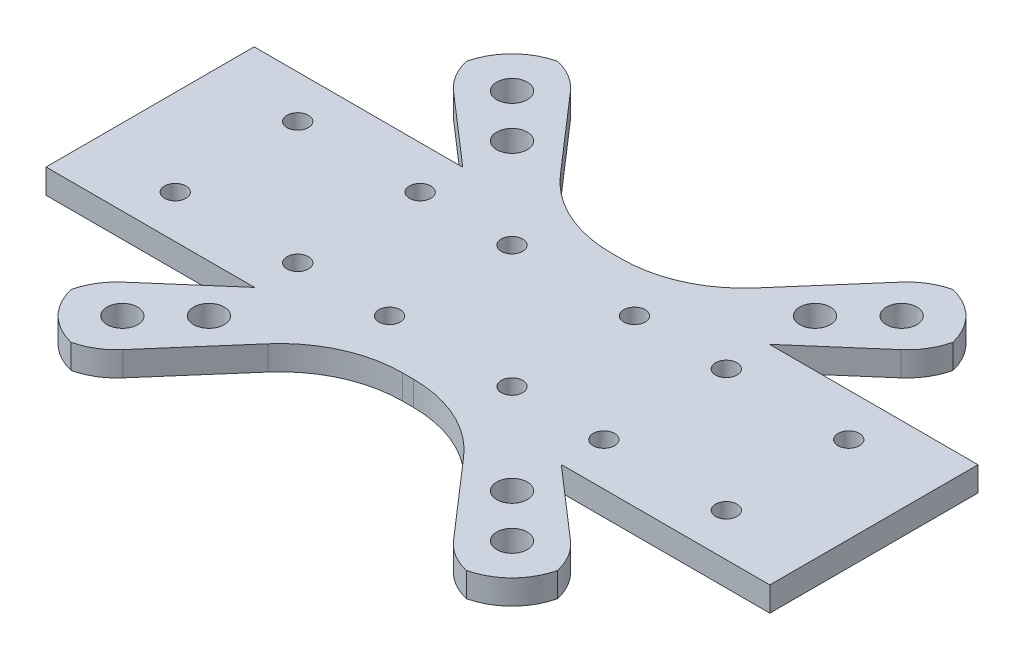
SolidWorks part; units mm, degrees
ref_plane "Front Plane" through (0, 0, 0) normal (0, 0, 1) x (1, 0, 0)
ref_plane "Top Plane" through (0, 0, 0) normal (0, 1, 0) x (1, 0, 0)
ref_plane "Right Plane" through (0, 0, 0) normal (1, 0, 0) x (0, 0, -1)
sketch "Sketch1" plane through (0, 0, 0) normal (0, 1, 0) x (1, 0, 0)
  line L1 (-15, -16) -> (15, -16) construction
  line L2 (-15, -16) -> (-15, 16) construction
  line L3 (-15, 16) -> (15, 16) construction
  line L4 (15, -16) -> (15, 16) construction
  line L5 (-15, -16) -> (15, 16) construction
  line L6 (-15, 16) -> (15, -16) construction
  line L7 (40, -40) -> (-40, -40)
  line L8 (40, -40) -> (40, 40)
  line L9 (40, 40) -> (-40, 40)
  line L10 (-40, -40) -> (-40, 40)
  line L11 (40, -40) -> (-40, 40) construction
  line L12 (40, 40) -> (-40, -40) construction
  line L13 (10, -10) -> (-10, -10) construction
  line L14 (10, -10) -> (10, 10) construction
  line L15 (10, 10) -> (-10, 10) construction
  line L16 (-10, -10) -> (-10, 10) construction
  line L17 (10, -10) -> (-10, 10) construction
  line L18 (10, 10) -> (-10, -10) construction
  circle A0 centre (-24.7487, 24.7487) radius 2.5
  circle A1 centre (24.7487, 24.7487) radius 2.5
  circle A2 centre (24.7487, -24.7487) radius 2.5
  circle A3 centre (-24.7487, -24.7487) radius 2.5
  circle A4 centre (-10, 10) radius 1.75
  circle A5 centre (10, 10) radius 1.75
  circle A6 centre (10, -10) radius 1.75
  circle A7 centre (-10, -10) radius 1.75
  circle A8 centre (31.8198, 31.8198) radius 2.5
  circle A9 centre (-31.8198, 31.8198) radius 2.5
  circle A10 centre (-31.8198, -31.8198) radius 2.5
  circle A11 centre (31.8198, -31.8198) radius 2.5
  point P0 (0, 0)
  point P6 (0, 0)
  point P19 (0, 0)
  dimension "D5" = 35
  dimension "D11" = 45
  dimension "D1" = 30
  dimension "D2" = 32
  dimension "D3" = 80
  dimension "D4" = 80
  dimension "D6" = 35
  dimension "D7" = 35
  dimension "D8" = 35
  dimension "D9" = 20
  dimension "D10" = 20
  dimension "D12" = 45
  dimension "D13" = 45
  dimension "D14" = 45
extrude "Boss-Extrude1" add sketch "Sketch1" along normal blind 4
sketch "Sketch2" plane through (0, 4, 0) normal (0, 1, 0) x (1, 0, 0)
  line L0 (-40, 30) -> (-40, -30)
  line L1 (15, -15) -> (-15, -15) construction
  line L2 (15, -15) -> (15, 15) construction
  line L3 (15, 15) -> (-15, 15) construction
  line L4 (-15, -15) -> (-15, 15) construction
  line L5 (15, -15) -> (-15, 15) construction
  line L6 (15, 15) -> (-15, -15) construction
  line L11 (-40, -30) -> (-17, -10)
  line L12 (-40, 40) -> (-40, -40) construction
  line L13 (-17, -10) -> (-17, 10)
  line L14 (-17, 10) -> (-40, 30)
  line L15 (40, 40) -> (-40, 40) construction
  line L16 (-40, -40) -> (40, -40) construction
  line L17 (30, 40) -> (-30, 40)
  line L18 (10, 17) -> (30, 40)
  line L19 (-10, 17) -> (10, 17)
  line L20 (-30, 40) -> (-10, 17)
  line L21 (40, -30) -> (40, 30)
  line L22 (17, -10) -> (40, -30)
  line L23 (17, 10) -> (17, -10)
  line L24 (40, 30) -> (17, 10)
  line L25 (-30, -40) -> (30, -40)
  line L26 (-10, -17) -> (-30, -40)
  line L27 (10, -17) -> (-10, -17)
  line L28 (30, -40) -> (10, -17)
  point P0 (0, 0)
  point P6 (-40, 0)
  point P32 (0, 0)
  dimension "D1" = 30
  dimension "D2" = 30
  dimension "D3" = 10
  dimension "D4" = 30
  dimension "D5" = 10
  dimension "D6" = 30
  dimension "D8" = 23
  dimension "D7" = 4
extrude "Cut-Extrude2" cut sketch "Sketch2" against normal through all
fillet "Fillet1" radius 10 12 edges at (-30, 2, 40) (-40, 2, 40) (-40, 2, 30) (-40, 2, -40) (-40, 2, -30) (-30, 2, -40) (30, 2, -40) (40, 2, -40) (40, 2, -30) (40, 2, 30) (40, 2, 40) (30, 2, 40)
fillet "Fillet2" radius 20 8 edges at (-17, 2, 10) (-17, 2, -10) (-10, 2, -17) (10, 2, -17) (17, 2, -10) (17, 2, 10) (10, 2, 17) (-10, 2, 17)
sketch "Sketch5" plane through (0, 4, 0) normal (0, 1, 0) x (1, 0, 0)
  line L0 (-0.8874, 17) -> (13.289, 12.1235)
  line L1 (-0.8874, 17) -> (59.1126, 17)
  line L2 (-0.8874, 17) -> (-0.8874, -17) construction
  line L3 (-0.8874, -17) -> (59.1126, -17)
  line L4 (59.1126, 17) -> (59.1126, -17)
  line L5 (13.289, 12.1235) -> (13.289, -13.4962)
  line L6 (13.289, -13.4962) -> (-0.8874, -17)
  dimension "D1" = 34
  dimension "D2" = 60
extrude "Boss-Extrude3" add sketch "Sketch5" against normal blind 4
sketch "Sketch6" plane through (0, 4, 0) normal (0, 1, 0) x (1, 0, 0)
  line L0 (10, 10) -> (35.6615, 10) construction
  line L2 (25, 10) -> (45, 10) construction
  line L3 (25, 10) -> (25, -10) construction
  line L4 (25, -10) -> (45, -10) construction
  line L5 (45, 10) -> (45, -10) construction
  circle A2 centre (25, 10) radius 1.75
  circle A4 centre (45, 10) radius 1.75
  circle A5 centre (25, -10) radius 1.75
  circle A6 centre (45, -10) radius 1.75
  dimension "D1" = 15
  dimension "D2" = 20
  dimension "D3" = 20
extrude "Cut-Extrude3" cut sketch "Sketch6" against normal blind 4
mirror "Mirror1" about plane through (0, 0, 0) normal (1, 0, 0) of "Cut-Extrude3", "Boss-Extrude3"
